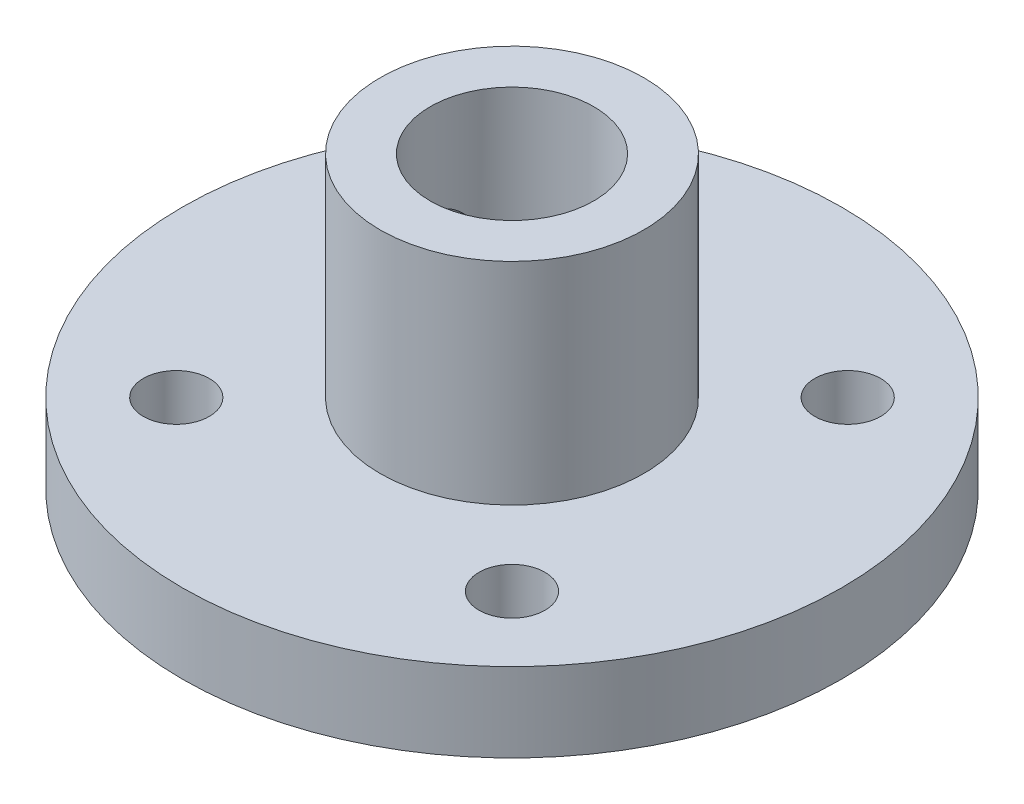
SolidWorks part; units mm, degrees
ref_plane "Alzado" through (0, 0, 0) normal (0, 0, 1) x (1, 0, 0)
ref_plane "Planta" through (0, 0, 0) normal (0, 1, 0) x (1, 0, 0)
ref_plane "Vista lateral" through (0, 0, 0) normal (1, 0, 0) x (0, 0, -1)
sketch "Croquis1" plane through (0, 0, 0) normal (0, 1, 0) x (1, 0, 0)
  line L0 (0, 0) -> (-6.6149, 6.6149) construction
  line L1 (-6.6149, 6.6149) -> (7.3418, -7.3418) construction
  line L2 (0, 0) -> (-6.786, -6.786) construction
  line L3 (-6.786, -6.786) -> (7.1299, 7.1299) construction
  circle A0 centre (0, 0) radius 12.5
  circle A1 centre (-6.364, 6.364) radius 1.25
  circle A3 centre (2.3431, -13.6569) radius 1.25
  circle A5 centre (0, 0) radius 3.1
  circle A6 centre (0, 0) radius 5
  circle A7 centre (6.364, 6.364) radius 1.25
  circle A8 centre (6.364, -6.364) radius 1.25
  circle A9 centre (-6.364, -6.364) radius 1.25
  point P14 (-1.6569, -4)
  point P23 (0, 0)
  dimension "D1" = 25
  dimension "D2" = 2.5
  dimension "D4" = 9
  dimension "D5" = 6.2
  dimension "D6" = 10
  dimension "D7" = 45
  dimension "D3" = 4
extrude "Saliente-Extruir1" add sketch "Croquis1" along normal blind 3 contours A0 A6 A3 A1 | A6 A5 | A5 region at (-12.1464, 0, 0) region at (0, 0, 0) region at (-4.8586, 0, 0)
extrude "Saliente-Extruir2" add sketch "Croquis1<3>" along normal blind 8 from surface contours A6 | A5 starting at face at (-6.364, 3, 7.614)
sketch "Croquis1<3>" plane through (0, 0, 0) normal (0, 1, 0) x (1, 0, 0) same geometry as "Croquis1"
sketch "Croquis2" plane through (0, 0, 0) normal (1, 0, 0) x (0, 0, -1)
  line L0 (3.1, 11) -> (-3.1, 11) construction
  circle A0 centre (0, 6) radius 1.5
  dimension "D1" = 3
  dimension "D2" = 5
extrude "Cortar-Extruir1" cut sketch "Croquis2" against normal through all
